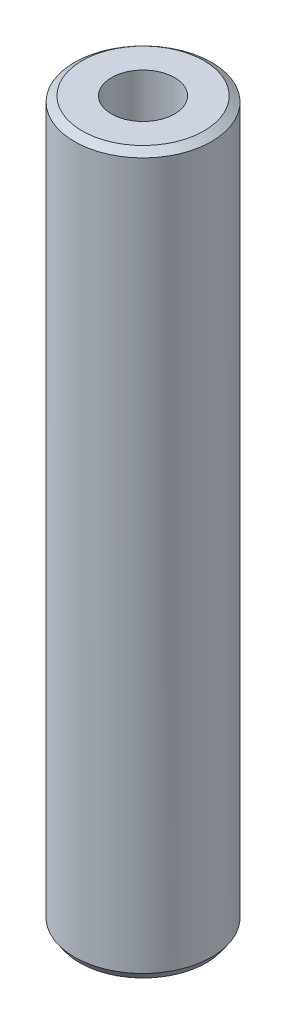
SolidWorks part; units mm, degrees
ref_plane "Front Plane" through (0, 0, 0) normal (0, 0, 1) x (1, 0, 0)
ref_plane "Top Plane" through (0, 0, 0) normal (0, 1, 0) x (1, 0, 0)
ref_plane "Right Plane" through (0, 0, 0) normal (1, 0, 0) x (0, 0, -1)
sketch "Sketch1" plane through (0, 0, 0) normal (0, 1, 0) x (1, 0, 0)
  circle A0 centre (0, 0) radius 40
  dimension "SHAFT_OD" = 80
extrude "Boss-Extrude1" add sketch "Sketch1" along normal blind 419.4666
sketch "Sketch2" plane through (0, 0, 0) normal (0, 1, 0) x (1, 0, 0)
  circle A0 centre (0, 0) radius 18.3952
  dimension "BORE_D" = 36.7904
extrude "Cut-Extrude1" cut sketch "Sketch2" along normal through all
chamfer "Chamfer1" distance 3.1146 angle 55.178 2 edges at (0, 419.4666, 40) (0, 0, 40) first distance on face at (0, 419.4666, 40) first distance on face at (0, 0, 18.3952)
